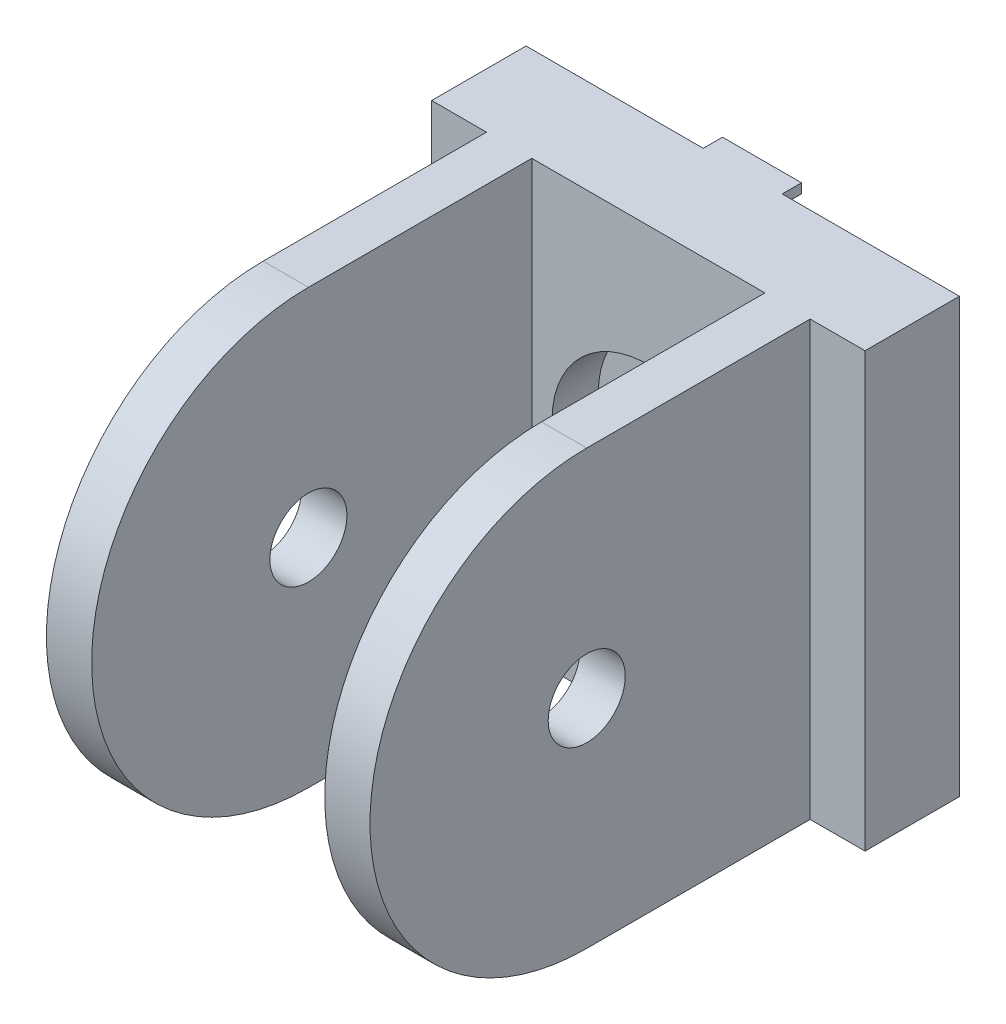
SolidWorks part; units mm, degrees
ref_plane "前视基准面" through (0, 0, 0) normal (0, 0, 1) x (1, 0, 0)
ref_plane "上视基准面" through (0, 0, 0) normal (0, 1, 0) x (1, 0, 0)
ref_plane "右视基准面" through (0, 0, 0) normal (1, 0, 0) x (0, 0, -1)
sketch "草图1" plane through (0, 0, 0) normal (0, 0, 1) x (1, 0, 0)
  line L1 (-22.5, -22.5) -> (22.5, -22.5)
  line L2 (-22.5, -22.5) -> (-22.5, 22.5)
  line L3 (-22.5, 22.5) -> (22.5, 22.5)
  line L4 (22.5, -22.5) -> (22.5, 22.5)
  line L5 (-22.5, -22.5) -> (22.5, 22.5) construction
  line L6 (-22.5, 22.5) -> (22.5, -22.5) construction
  point P0 (0, 0)
  dimension "D1" = 45
  dimension "D2" = 45
extrude "凸台-拉伸1" add sketch "草图1" along normal blind 9.8
sketch "草图2" plane through (0, 0, 9.8) normal (0, 0, 1) x (1, 0, 0)
  line L0 (22.5, 22.5) -> (-22.5, 22.5) construction
  line L1 (-16.8, -22.5) -> (-12.1, -22.5)
  line L2 (-16.8, -22.5) -> (-16.8, 22.5)
  line L3 (-16.8, 22.5) -> (-12.1, 22.5)
  line L4 (-12.1, -22.5) -> (-12.1, 22.5)
  line L5 (-16.8, -22.5) -> (-12.1, 22.5) construction
  line L6 (-16.8, 22.5) -> (-12.1, -22.5) construction
  line L7 (-22.5, 22.5) -> (-22.5, -22.5) construction
  line L8 (0, 0) -> (0, 12.1648) construction
  line L9 (16.8, -22.5) -> (12.1, -22.5)
  line L10 (16.8, -22.5) -> (16.8, 22.5)
  line L11 (12.1, -22.5) -> (12.1, 22.5)
  line L12 (16.8, 22.5) -> (12.1, 22.5)
  line L13 (-22.5, -22.5) -> (22.5, -22.5) construction
  point P0 (-14.45, 0)
  dimension "D1" = 4.7
  dimension "D2" = 5.7
extrude "凸台-拉伸2" add sketch "草图2" along normal blind 45.7
sketch "草图3" plane through (-16.8, 0, 0) normal (-1, 0, 0) x (0, 0, 1)
  line L0 (55.5, 22.5) -> (55.5, -22.5) construction
  line L1 (55.5, 22.5) -> (9.8, 22.5) construction
  line L2 (55.5, -22.5) -> (9.8, -22.5) construction
  arc A0 (33, -22.5) -> (33, 22.5) centre (33, 0) ccw
  dimension "D1" = 45
extrude "切除-拉伸2" cut sketch "草图3" against normal through all and the other way through all flip side to cut
sketch "草图4" plane through (-16.8, 0, 0) normal (-1, 0, 0) x (0, 0, 1)
  circle A0 centre (33, 0) radius 4
  dimension "D1" = 8
extrude "切除-拉伸3" cut sketch "草图4" against normal through all
sketch "草图6" plane through (0, 0, 9.8) normal (0, 0, 1) x (1, 0, 0)
  circle A0 centre (0, 0) radius 6.1
  dimension "D1" = 12.2
extrude "切除-拉伸5" cut sketch "草图6" against normal through all
sketch "草图7" plane through (0, 0, 0) normal (0, 0, -1) x (-1, 0, 0)
  line L0 (0, 0) -> (-17.0155, 0) construction
  line L1 (-22.5, 22.5) -> (22.5, 22.5) construction
  line L2 (-4.1, 22.5) -> (4.1, 22.5)
  line L3 (-4.1, 22.5) -> (-4.1, 21.5)
  line L4 (-4.1, 21.5) -> (4.1, 21.5)
  line L5 (4.1, 22.5) -> (4.1, 21.5)
  line L6 (4.1, -22.5) -> (4.1, -21.5)
  line L7 (-4.1, -22.5) -> (-4.1, -21.5)
  line L8 (-4.1, -21.5) -> (4.1, -21.5)
  line L9 (-4.1, -22.5) -> (4.1, -22.5)
  point P9 (0, 22.5)
  point P10 (0, 22.5)
  dimension "D1" = 1
  dimension "D2" = 8.2
extrude "凸台-拉伸3" add sketch "草图7" along normal blind 2
sketch "草图8" plane through (0, 0, 9.8) normal (0, 0, 1) x (1, 0, 0)
  circle A0 centre (0, 0) radius 10
extrude "切除-拉伸6" cut sketch "草图8" against normal blind 4.8
